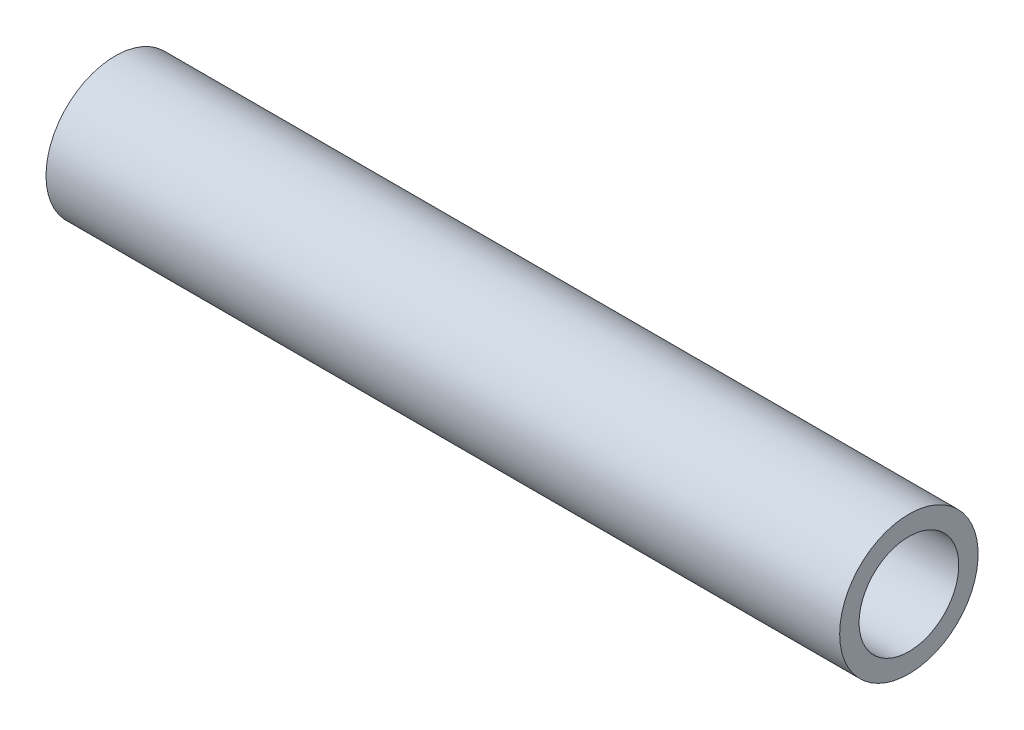
SolidWorks part; units mm, degrees
ref_plane "Front Plane" through (0, 0, 0) normal (0, 0, 1) x (1, 0, 0)
ref_plane "Top Plane" through (0, 0, 0) normal (0, 1, 0) x (1, 0, 0)
ref_plane "Right Plane" through (0, 0, 0) normal (1, 0, 0) x (0, 0, -1)
sketch "Tube_T4_Stub Sketch" plane through (0, 0, 0) normal (0, 0, 1) x (1, 0, 0)
  line L0 (-1000, 0) -> (1000, 0) construction
  line L1 (-18.2, 2.286) -> (-18.2, 3.175)
  line L2 (-18.2, 3.175) -> (18.2, 3.175)
  line L3 (18.2, 3.175) -> (18.2, 2.286)
  line L4 (18.2, 2.286) -> (-18.2, 2.286)
revolve "Tube_T4_Stub" add sketch "Tube_T4_Stub Sketch" angle 360 about L0
ref_axis "Engine Axis" through (20.02, 0, 0) along (-1, 0, 0)
